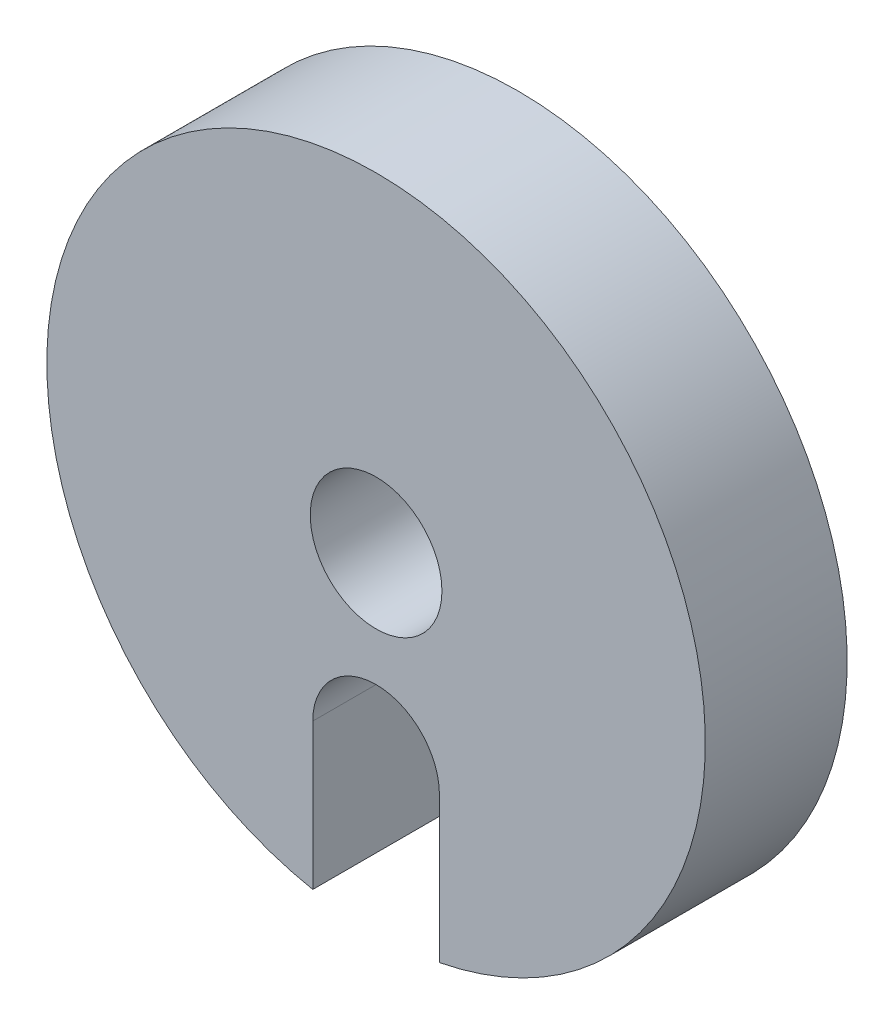
SolidWorks part; units mm, degrees
material "ABS"
ref_plane "Płaszczyzna przednia" through (0, 0, 0) normal (0, 0, 1) x (1, 0, 0)
ref_plane "Płaszczyzna górna" through (0, 0, 0) normal (0, 1, 0) x (1, 0, 0)
ref_plane "Płaszczyzna prawa" through (0, 0, 0) normal (1, 0, 0) x (0, 0, -1)
sketch "Szkic1" plane through (0, 0, 0) normal (0, 0, 1) x (1, 0, 0)
  line L0 (-2.5, -7) -> (-2.5, -12.7574)
  line L1 (2.5, -7) -> (2.5, -12.7574)
  circle A0 centre (0, 0) radius 13
  circle A1 centre (0, 0) radius 2.6
  arc A2 (2.5, -7) -> (-2.5, -7) centre (0, -7) ccw
  dimension "D1" = 26
  dimension "D2" = 5.2
  dimension "D3" = 5
  dimension "D4" = 7
extrude "Dodanie-wyciągnięcie1" add sketch "Szkic1" along normal blind 5.6 contours A2 L1 A0 L0 A1 region at (-2.866, -9.8787, 0)
